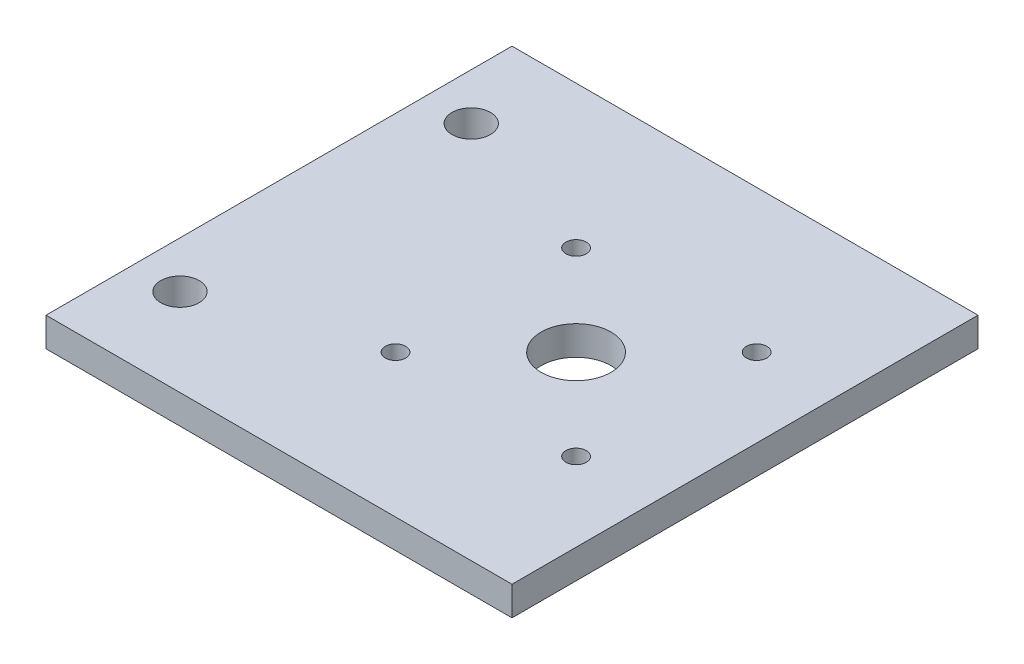
SolidWorks part; units mm, degrees
material "Lega 1060"
ref_plane "Piano frontale" through (0, 0, 0) normal (0, 0, 1) x (1, 0, 0)
ref_plane "Piano superiore" through (0, 0, 0) normal (0, 1, 0) x (1, 0, 0)
ref_plane "Piano destro" through (0, 0, 0) normal (1, 0, 0) x (0, 0, -1)
sketch "Schizzo1" plane through (0, 0, 0) normal (0, 0, 1) x (1, 0, 0)
  line L1 (0, 0) -> (80, 0)
  line L2 (0, 0) -> (0, 5)
  line L3 (0, 5) -> (80, 5)
  line L4 (80, 0) -> (80, 5)
  dimension "D1" = 5
  dimension "D2" = 80
extrude "Estrusione-Estrusione1" add sketch "Schizzo1" along normal blind 80
hole_wizard "Foro per Vite M6-1" positions "Schizzo3" profile "Schizzo2" hole size "M6" standard "ISO" end condition through all
sketch "Schizzo3" plane through (0, 5, 0) normal (0, 1, 0) x (1, 0, 0)
  line L0 (-9.8996, -40) -> (95.021, -40) construction
  line L2 (80, -80) -> (0, -80) construction
  line L3 (80, 0) -> (0, 0) construction
  line L4 (0, -80) -> (0, 0) construction
  point P0 (8, -15)
  point P1 (8, -65)
  dimension "D1" = 15
  dimension "D2" = 8
sketch "Schizzo2" plane through (8, 5, 15) normal (1, 0, 0) x (0, 0, 1)
  line L0 (0, 0) -> (0, 5)
  line L1 (0, 5) -> (3.3, 5)
  line L2 (3.3, 5) -> (3.3, 0)
  line L5 (3.3, 0) -> (0, 0)
  line L11 (0, -6.35) -> (0, 107.95) construction
  dimension "Thru Hole Dia." = 6.6
  dimension "Thru Hole Depth" = 5
sketch "Schizzo4" plane through (0, 5, 0) normal (0, 1, 0) x (1, 0, 0)
  line L3 (19.8289, -40) -> (54.8798, -40) construction
  line L4 (80, -80) -> (0, -80) construction
  line L5 (80, 0) -> (0, 0) construction
  circle A0 centre (51, -40) radius 6
  circle A1 centre (8, -15) radius 3.3 construction
  dimension "D1" = 12
  dimension "D2" = 43
extrude "Taglio-Estrusione1" cut sketch "Schizzo4" against normal through all
sketch "Schizzo6" plane through (0, 5, 0) normal (0, 1, 0) x (1, 0, 0)
  line L0 (42.0101, -40) -> (55.783, -40) construction
  line L1 (51, -40) -> (51, -30.1482) construction
  line L2 (80, -80) -> (0, -80) construction
  line L3 (80, 0) -> (0, 0) construction
  circle A0 centre (35.5, -24.5) radius 1.75
  circle A1 centre (66.5, -24.5) radius 1.75
  circle A2 centre (66.5, -55.5) radius 1.75
  circle A3 centre (35.5, -55.5) radius 1.75
  dimension "D1" = 3.5
  dimension "D2" = 31
  dimension "D3" = 31
extrude "Taglio-Estrusione3" cut sketch "Schizzo6" against normal through all
